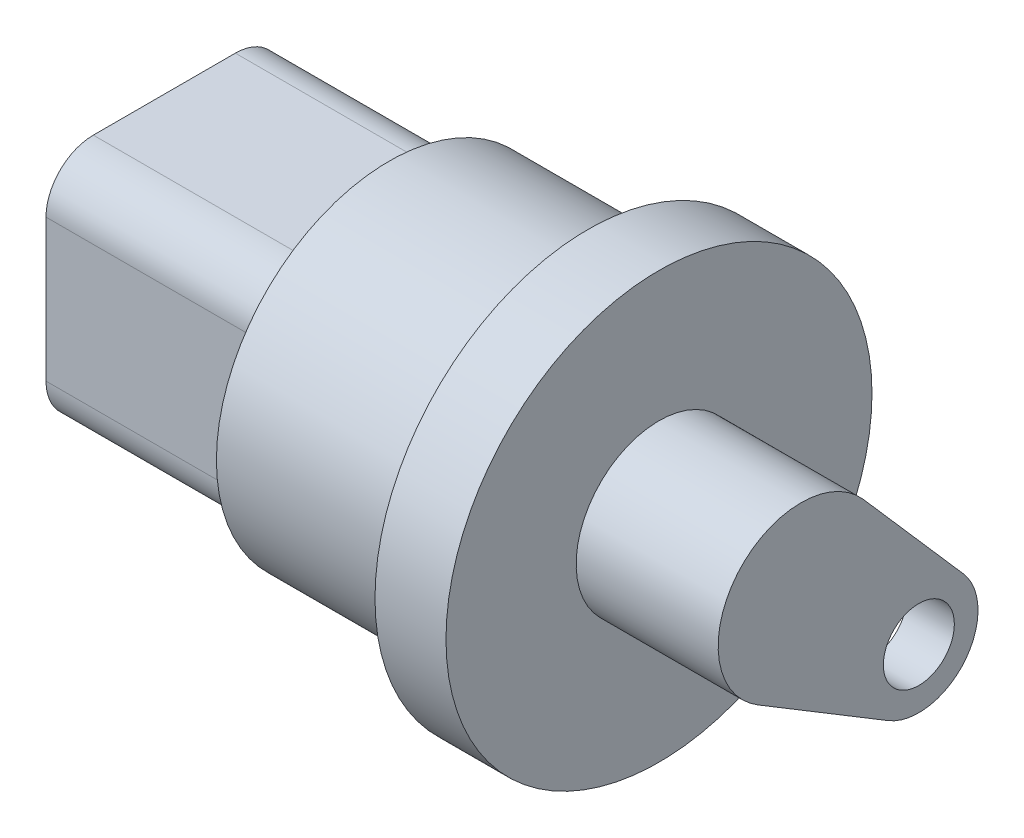
SolidWorks part; units mm, degrees
ref_plane "Front Plane" through (0, 0, 0) normal (0, 0, 1) x (1, 0, 0)
ref_plane "Top Plane" through (0, 0, 0) normal (0, 1, 0) x (1, 0, 0)
ref_plane "Right Plane" through (0, 0, 0) normal (1, 0, 0) x (0, 0, -1)
sketch "Sketch2" plane through (0, 0, 0) normal (1, 0, 0) x (0, 0, -1)
  line L1 (-5, 5) -> (5, 5)
  line L2 (-5, 5) -> (-5, -5)
  line L3 (-5, -5) -> (5, -5)
  line L4 (5, 5) -> (5, -5)
  line L5 (-5, 5) -> (5, -5) construction
  line L6 (-5, -5) -> (5, 5) construction
  circle A0 centre (0, 0) radius 7.3
  circle A1 centre (0, 0) radius 9
  dimension "D1" = 14.6
  dimension "D4" = 18
  dimension "D2" = 10
  dimension "D3" = 10
extrude "Boss-Extrude1" add sketch "Sketch2" along normal blind 3 contours A1
extrude "Boss-Extrude2" add sketch "Sketch2<4>" against normal blind 8.4 contours A0
sketch "Sketch2<4>" plane through (0, 0, 0) normal (1, 0, 0) x (0, 0, -1) same geometry as "Sketch2"
extrude "Boss-Extrude3" add sketch "Sketch2<6>" against normal blind 9.5 from surface contours L4 L3 L2 L1 starting at face at (-8.4, 0, -7.3)
sketch "Sketch2<6>" plane through (0, 0, 0) normal (1, 0, 0) x (0, 0, -1) same geometry as "Sketch2"
sketch "Sketch6" plane through (0, 0, 0) normal (1, 0, 0) x (0, 0, -1)
  line L0 (-5, -5) -> (5, 5) construction
  line L1 (0, 0) -> (8.6111, -7.2256) construction
  line L2 (2.6355, 2.3031) -> (6.8618, -2.533)
  line L4 (-1.8105, -2.9954) -> (3.6861, -6.3177)
  line L5 (0, 0) -> (0, -13.1884) construction
  circle A0 centre (4.9793, -4.1781) radius 2.5
  circle A1 centre (0, 0) radius 9
  circle A2 centre (0, 0) radius 9 construction
  circle A3 centre (0, 0) radius 3.5
  circle A4 centre (4.9793, -4.1781) radius 1.5
  dimension "D2" = 5
  dimension "D3" = 7
  dimension "D4" = 3
  dimension "D1" = 50
extrude "Boss-Extrude6" add sketch "Sketch6" along normal blind 4 from surface contours A3 starting at face at (3, 0, -9)
extrude "Boss-Extrude7" add sketch "Sketch6<4>" along normal blind 2 from surface contours A3 L4 A0 L2 | A3 | A0 A4 region at (0, -2.4234, -2.8881) region at (0, 0, 0) region at (0, -3.3244, -7.2536) starting at face at (7, 0, -3.5)
sketch "Sketch6<4>" plane through (0, 0, 0) normal (1, 0, 0) x (0, 0, -1) same geometry as "Sketch6"
extrude "Cut-Extrude1" cut sketch "Sketch6<5>" against normal up to surface from surface contours A4 L1 | L1 A4 region at (0, -4.1781, -4.9793) up to face at (0, 0, -7.3) starting at face at (3, 0, -3.5)
sketch "Sketch6<5>" plane through (0, 0, 0) normal (1, 0, 0) x (0, 0, -1) same geometry as "Sketch6"
fillet "Fillet1" radius 2 4 edges at (-13.15, 5, 5) (-13.15, -5, 5) (-13.15, -5, -5) (-13.15, 5, -5)
